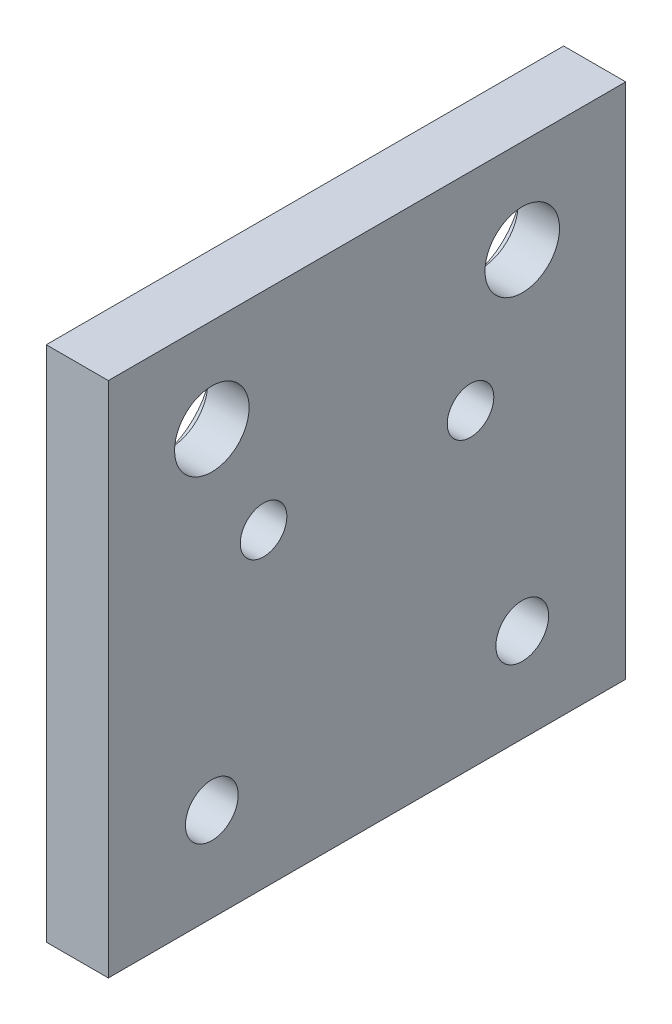
SolidWorks part; units mm, degrees
ref_plane "Front" through (0, 0, 0) normal (0, 0, 1) x (1, 0, 0)
ref_plane "Top" through (0, 0, 0) normal (0, 1, 0) x (1, 0, 0)
ref_plane "Right" through (0, 0, 0) normal (1, 0, 0) x (0, 0, -1)
sketch "Sketch2" plane through (0, 0, 0) normal (1, 0, 0) x (0, 0, -1)
  line L1 (-25, -25) -> (25, -25)
  line L2 (-25, -25) -> (-25, 25)
  line L3 (-25, 25) -> (25, 25)
  line L4 (25, -25) -> (25, 25)
  line L5 (0, 25) -> (0, -25) construction
  line L6 (-25, 0) -> (25, 0) construction
  point P0 (0, 0)
  dimension "D1" = 50
  dimension "D2" = 50
extrude "Boss-Extrude1" add sketch "Sketch2" along normal blind 6
sketch "Sketch6" plane through (0, 0, 0) normal (1, 0, 0) x (0, 0, -1)
  line L1 (15, -15.95) -> (-15, -15.95) construction
  line L2 (15, -15.95) -> (15, 15.95) construction
  line L3 (15, 15.95) -> (-15, 15.95) construction
  line L4 (-15, -15.95) -> (-15, 15.95) construction
  line L5 (0, 15.95) -> (0, -15.95) construction
  line L6 (15, 0) -> (-15, 0) construction
  circle A0 centre (-15, 15.95) radius 3.6
  circle A1 centre (15, 15.95) radius 3.6
  circle A2 centre (-15, -15.95) radius 2.55
  circle A3 centre (15, -15.95) radius 2.55
  point P0 (0, 0)
  dimension "D3" = 7.2
  dimension "D4" = 5.1
  dimension "D1" = 31.9
  dimension "D2" = 30
extrude "Cut-Extrude2" cut sketch "Sketch6" along normal through all
sketch "Sketch7" plane through (0, 0, 0) normal (-1, 0, 0) x (0, 0, 1)
  circle A0 centre (-15, -15.95) radius 5.05
  circle A1 centre (15, -15.95) radius 5.05
  circle A2 centre (-15, 15.95) radius 6
  circle A3 centre (15, 15.95) radius 6
  dimension "D1" = 12
  dimension "D2" = 10.1
extrude "Cut-Extrude3" cut sketch "Sketch7" against normal blind 2
hole_wizard "M4 Clearance Hole1" positions "Sketch11" profile "Sketch12" hole size "M4" standard "ANSI Metric" end condition through all
sketch "Sketch11" plane through (6, 0, 0) normal (1, 0, 0) x (0, 0, -1)
  line L2 (-10, 5) -> (10, 5) construction
  line L5 (0, 0) -> (0, 5) construction
  point P0 (-10, 5)
  point P2 (10, 5)
  dimension "D1" = 20
  dimension "D2" = 5
sketch "Sketch12" plane through (6, 5, 10) normal (0, 1, 0) x (0, 0, -1)
  line L0 (0, 0) -> (0, 6)
  line L1 (0, 6) -> (2.25, 6)
  line L2 (2.25, 6) -> (2.25, 0)
  line L5 (2.25, 0) -> (0, 0)
  line L11 (0, -6.35) -> (0, 107.95) construction
  dimension "Thru Hole Dia." = 4.5
  dimension "Thru Hole Depth" = 6
